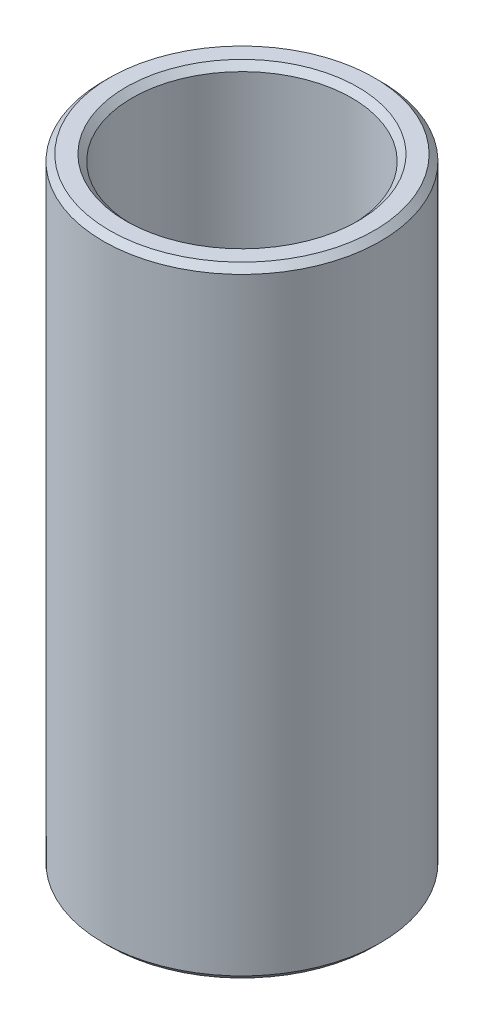
SolidWorks part; units mm, degrees
ref_plane "Front Plane" through (0, 0, 0) normal (0, 0, 1) x (1, 0, 0)
ref_plane "Top Plane" through (0, 0, 0) normal (0, 1, 0) x (1, 0, 0)
ref_plane "Right Plane" through (0, 0, 0) normal (1, 0, 0) x (0, 0, -1)
sketch "Sketch1" plane through (0, 0, 0) normal (0, 1, 0) x (1, 0, 0)
  circle A0 centre (0, 0) radius 52.5
  dimension "SLEEVE_OD" = 105
extrude "Boss-Extrude1" add sketch "Sketch1" along normal blind 234.8488
sketch "Sketch2" plane through (0, 0, 0) normal (0, 1, 0) x (1, 0, 0)
  circle A0 centre (0, 0) radius 41.5926
  dimension "BORE_D" = 83.1852
extrude "Cut-Extrude1" cut sketch "Sketch2" along normal through all
chamfer "Chamfer1" distance 2.3567 angle 45 4 edges at (0, 234.8488, 41.5926) (0, 0, 41.5926) (0, 0, 52.5) (0, 234.8488, 52.5)
